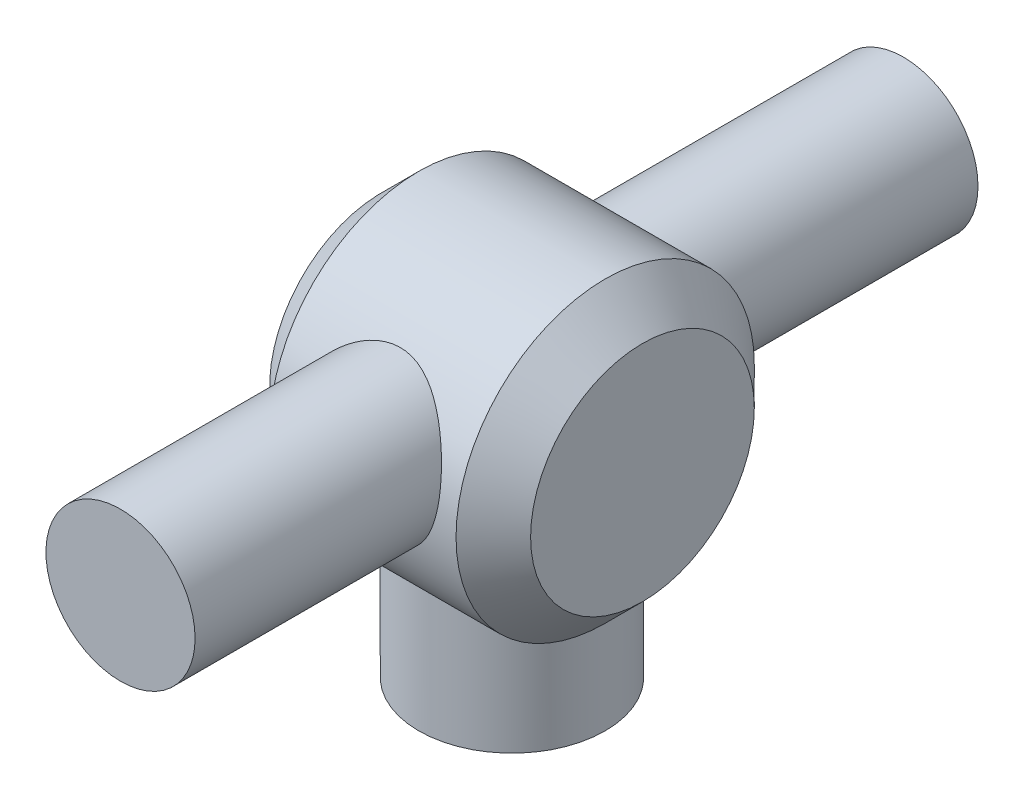
SolidWorks part; units mm, degrees
ref_plane "Front Plane" through (0, 0, 0) normal (0, 0, 1) x (1, 0, 0)
ref_plane "Top Plane" through (0, 0, 0) normal (0, 1, 0) x (1, 0, 0)
ref_plane "Right Plane" through (0, 0, 0) normal (1, 0, 0) x (0, 0, -1)
sketch "Sketch1" plane through (0, 0, 0) normal (0, 1, 0) x (1, 0, 0)
  circle A0 centre (0, 0) radius 5
  dimension "D1" = 10
extrude "Boss-Extrude1" add sketch "Sketch1" along normal blind 10
sketch "Sketch2" plane through (0, 0, 0) normal (1, 0, 0) x (0, 0, -1)
  circle A0 centre (0, 13) radius 8
  dimension "D1" = 16
  dimension "D2" = 13
extrude "Boss-Extrude2" add sketch "Sketch2" along normal mid plane 14
sketch "Sketch3" plane through (0, 0, 0) normal (0, 0, 1) x (1, 0, 0)
  circle A0 centre (0, 14.3054) radius 4
  dimension "D1" = 8
extrude "Boss-Extrude3" add sketch "Sketch3" along normal mid plane 42
chamfer "Chamfer1" distance 2 angle 45 2 edges at (7, 13, -8) (-7, 13, -8)
